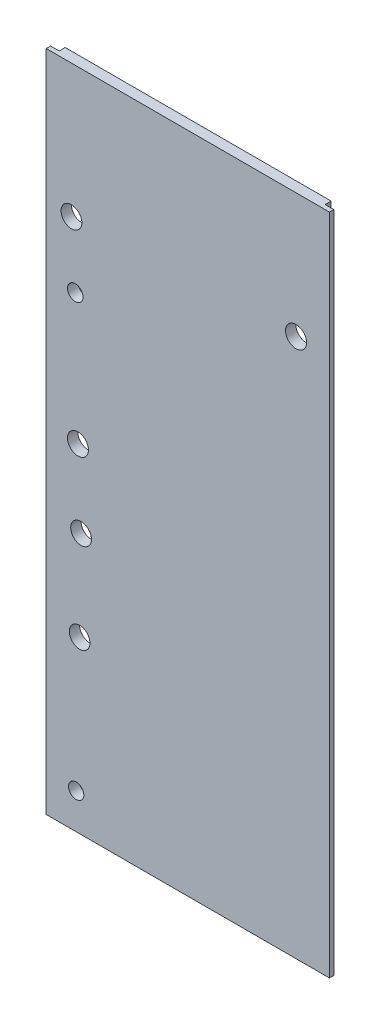
SolidWorks part; units mm, degrees
ref_plane "Front Plane" through (0, 0, 0) normal (0, 0, 1) x (1, 0, 0)
ref_plane "Top Plane" through (0, 0, 0) normal (0, 1, 0) x (1, 0, 0)
ref_plane "Right Plane" through (0, 0, 0) normal (1, 0, 0) x (0, 0, -1)
sketch "Sketch1" plane through (0, 0, 0) normal (0, 0, 1) x (1, 0, 0)
  line L1 (0, 0) -> (-488.95, 0)
  line L2 (0, 0) -> (0, -1219.2)
  line L3 (0, -1219.2) -> (-488.95, -1219.2)
  line L4 (-488.95, 0) -> (-488.95, -1219.2)
  line L5 (-488.95, 0) -> (-504.78, 0)
  line L6 (-488.95, 0) -> (-488.95, -1219.2)
  line L7 (-488.95, -1219.2) -> (-504.78, -1219.2)
  line L8 (-504.78, 0) -> (-504.78, -1219.2)
  line L9 (0, 0) -> (15.83, 0)
  line L10 (0, 0) -> (0, -1219.2)
  line L11 (0, -1219.2) -> (15.83, -1219.2)
  line L12 (15.83, 0) -> (15.83, -1219.2)
  circle A0 centre (-45.58, -228.93) radius 19.38
  circle A1 centre (-458.365, -244.56) radius 19.135
  circle A2 centre (-451.35, -361.9225) radius 14.26
  circle A3 centre (-446.415, -600.29) radius 19.265
  circle A4 centre (-440.665, -739.81) radius 19.085
  circle A5 centre (-443.355, -906.4175) radius 19.005
  circle A6 centre (-449.645, -1153.86) radius 14.035
  point P23 (0, 0)
  dimension "D4" = 38.76
  dimension "D5" = 38.27
  dimension "D6" = 28.52
  dimension "D7" = 38.53
  dimension "D8" = 38.17
  dimension "D9" = 38.01
  dimension "D10" = 28.07
  dimension "D1" = 488.95
  dimension "D2" = 1219.2
  dimension "D3" = 15.83
  dimension "D11" = 45.58
  dimension "D12" = 30.585
  dimension "D13" = 37.6
  dimension "D14" = 42.535
  dimension "D15" = 48.285
  dimension "D16" = 45.595
  dimension "D17" = 39.305
  dimension "D18" = 1153.86
  dimension "D19" = 906.4175
  dimension "D20" = 739.81
  dimension "D21" = 600.29
  dimension "D22" = 361.9225
  dimension "D23" = 244.56
  dimension "D24" = 228.93
extrude "Boss-Extrude1" add sketch "Sketch1" along normal blind 19.05 contours L1 L4 L3 L2 | L5 L8 L7 L4 | L12 L9 L2 L11 region at (-242.852, -609.9659, 0) region at (7.915, -609.6, 0) region at (-496.865, -609.6, 0)
extrude "Cut-Extrude1" cut sketch "Sketch1<3>" along normal blind 11.05 contours L5 L8 L7 L4 | L12 L9 L2 L11 region at (7.915, -609.6, 0) region at (-496.865, -609.6, 0)
sketch "Sketch1<3>" plane through (0, 0, 0) normal (0, 0, 1) x (1, 0, 0) same geometry as "Sketch1"
